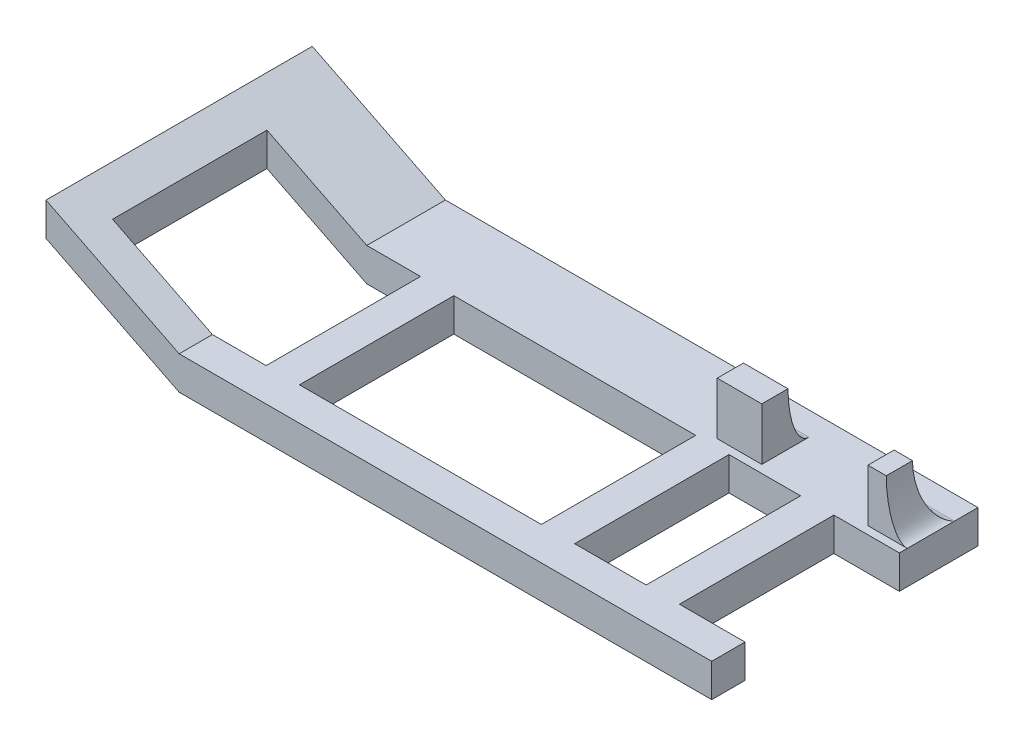
SolidWorks part; units mm, degrees
ref_plane "Front" through (0, 0, 0) normal (0, 0, 1) x (1, 0, 0)
ref_plane "Top" through (0, 0, 0) normal (0, 1, 0) x (1, 0, 0)
ref_plane "Right" through (0, 0, 0) normal (1, 0, 0) x (0, 0, -1)
sketch "Sketch1" plane through (0, 0, 0) normal (0, 1, 0) x (1, 0, 0)
  line L0 (0, 71.6) -> (203.2, 71.6)
  line L1 (0, 0) -> (203.2, 0)
  line L2 (0, 0) -> (0, 101.6)
  line L3 (0, 101.6) -> (203.2, 101.6)
  line L4 (203.2, 0) -> (203.2, 101.6)
  line L5 (0, 12.7) -> (203.2, 12.7)
  line L6 (138.2, 71.6) -> (138.2, 12.7)
  line L7 (178.2, 71.6) -> (178.2, 12.7)
  line L8 (178.2, 12.7) -> (165.5, 12.7)
  line L9 (165.5, 12.7) -> (165.5, 71.6)
  line L10 (165.5, 71.6) -> (125.5, 71.6)
  line L11 (125.5, 71.6) -> (125.5, 12.7)
  line L12 (125.5, 12.7) -> (20.5, 12.7)
  line L13 (20.5, 12.7) -> (20.5, 71.6)
  line L14 (20.5, 71.6) -> (33.2, 71.6)
  line L15 (33.2, 71.6) -> (33.2, 12.7)
  point P21 (33.2, 42.15)
  dimension "D1" = 203.2
  dimension "D2" = 101.6
  dimension "D3" = 30
  dimension "D4" = 12.7
  dimension "D5" = 12.7
  dimension "D6" = 12.7
  dimension "D7" = 12.7
  dimension "D8" = 25
  dimension "D9" = 65
  dimension "D10" = 170
extrude "Boss-Extrude1" add sketch "Sketch1" along normal blind 12.7 contours L0 L4 L3 L2 | L15 L0 L13 L5 | L0 L11 L5 L6 | L9 L5 L7 L0 | L5 L2 L1 L4 L12 region at (101.6, 0, -86.6) region at (26.85, 0, -42.15) region at (101.6, 0, -6.35) region at (131.85, 0, -42.15) region at (171.85, 0, -42.15)
sketch "Sketch2" plane through (0, 0, -101.6) normal (0, 0, -1) x (-1, 0, 0)
  line L0 (0, 12.7) -> (50.8, 38.1)
  line L1 (50.8, 38.1) -> (50.8, 25.4)
  line L2 (50.8, 25.4) -> (0, 0)
  line L7 (-203.2, 0) -> (0, 0)
  line L8 (0, 0) -> (0, 12.7)
  line L9 (0, 12.7) -> (-203.2, 12.7)
  line L10 (-203.2, 12.7) -> (-203.2, 0)
  line L11 (-203.2, 0) -> (0, 0)
  line L13 (0, 12.7) -> (-203.2, 12.7)
  line L14 (-203.2, 12.7) -> (-203.2, 0)
  dimension "D1" = 12.7
  dimension "D2" = 50.8
  dimension "D3" = 25.4
  dimension "D4" = 0
extrude "Boss-Extrude2" add sketch "Sketch2" against normal blind 30
ref_plane "Plane1" through (0, 0, -50.8) normal (0, 0, -1) x (-1, 0, 0)
sketch "Sketch4" plane through (0, 0, 0) normal (0, 0, 1) x (1, 0, 0)
  line L0 (0, 12.7) -> (-50.8, 38.1)
  line L1 (-50.8, 38.1) -> (-50.8, 25.4)
  line L2 (-50.8, 25.4) -> (0, 0)
  line L3 (0, 12.7) -> (0, 0)
  dimension "D1" = 12.7
  dimension "D2" = 50.8
  dimension "D3" = 25.4
extrude "Boss-Extrude3" add sketch "Sketch4" against normal blind 12.7
sketch "Sketch5" plane through (0, 0, -71.6) normal (0, 0, 1) x (1, 0, 0)
  line L0 (-50.8, 38.1) -> (-50.8, 25.4)
  line L1 (-50.8, 25.4) -> (-38.1, 19.05)
  line L2 (0, 0) -> (-50.8, 25.4) construction
  line L3 (-38.1, 19.05) -> (-38.1, 31.75)
  line L4 (-50.8, 38.1) -> (0, 12.7) construction
  line L5 (-38.1, 31.75) -> (-50.8, 38.1)
  dimension "D1" = 12.7
extrude "Boss-Extrude4" add sketch "Sketch5" along normal up to next
sketch "Sketch6" plane through (0, 12.7, 0) normal (0, 1, 0) x (1, 0, 0)
  line L0 (203.2, 74.6) -> (174.5417, 74.6)
  line L1 (203.2, 71.6) -> (203.2, 101.6) construction
  line L2 (178.2, 71.6) -> (203.2, 71.6) construction
  line L3 (188.2, 74.6) -> (188.2, 84.6)
  line L4 (188.2, 84.6) -> (195.2, 84.6)
  line L5 (195.2, 84.6) -> (195.2, 74.6)
  line L6 (147.7, 74.6) -> (147.7, 84.6)
  line L7 (147.7, 84.6) -> (130.7, 84.6)
  line L8 (130.7, 84.6) -> (130.7, 74.6)
  line L9 (130.7, 74.6) -> (147.7, 74.6)
  point P6 (190.7, 71.6)
  point P15 (188.2, 79.6)
  dimension "D1" = 3
  dimension "D2" = 7
  dimension "D3" = 10
  dimension "D4" = 10
  dimension "D5" = 17
  dimension "D6" = 40.5
  dimension "D7" = 15
  dimension "D8" = 0
extrude "Boss-Extrude5" add sketch "Sketch6" along normal blind 20 contours L8 L9 L6 L7 | L5 L4 L3 L0 region at (191.7, 12.7, -79.6) region at (139.2, 12.7, -79.6)
fillet "Fillet4" radius 8 2 edges at (191.7, 12.7, -84.6) (195.2, 12.7, -79.6) second distance 20 first distance on face at (191.7, 12.7, -79.6)
fillet "Fillet5" radius 8 1 edges at (139.2, 12.7, -84.6) second distance 20 first distance on face at (151.85, 12.7, -42.15)
